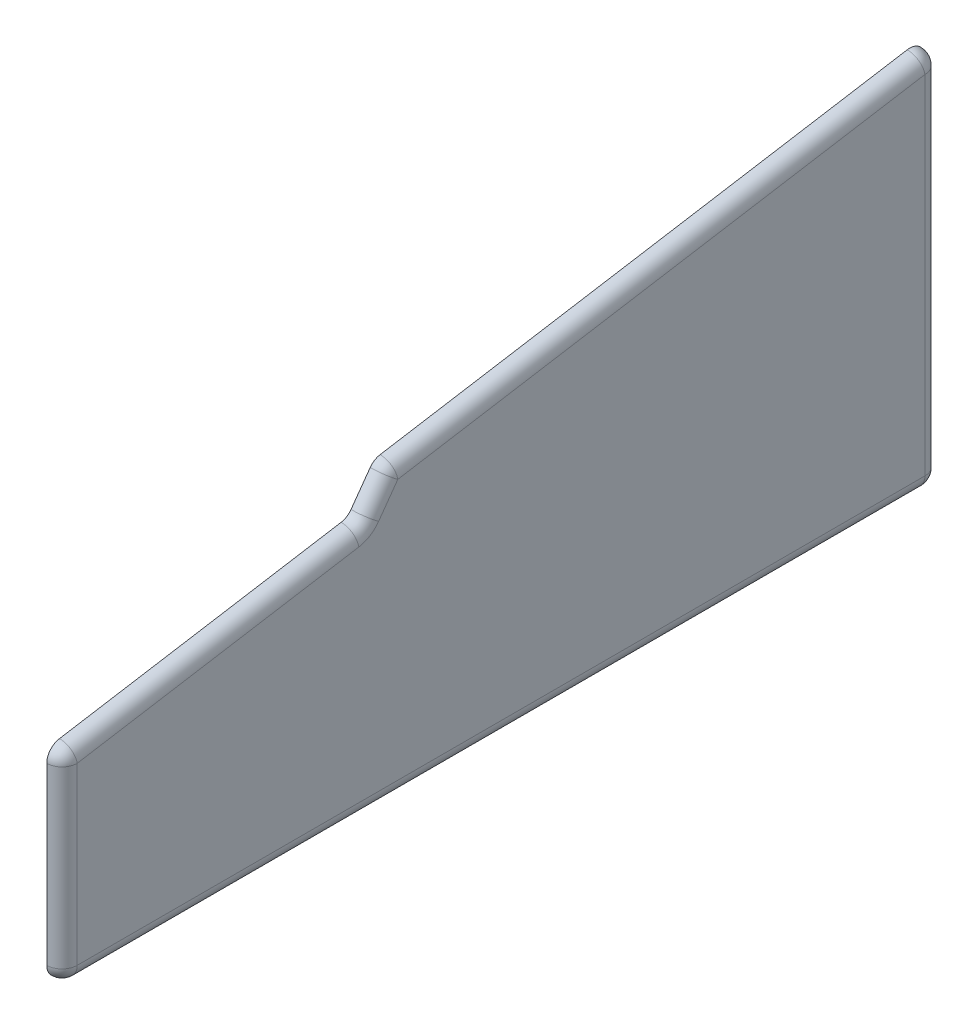
SolidWorks part; units mm, degrees
note: The reader was unsure of these and kept them because the rebuilt part matched: shared geometry of "Sketch1<4>".
ref_plane "Front Plane" through (0, 0, 0) normal (0, 0, 1) x (1, 0, 0)
ref_plane "Top Plane" through (0, 0, 0) normal (0, 1, 0) x (1, 0, 0)
ref_plane "Right Plane" through (0, 0, 0) normal (1, 0, 0) x (0, 0, -1)
sketch "Sketch1" plane through (-329.9746, 0, 0) normal (-1, 0, 0) x (0, 0, 1)
  line L0 (-32.649, -10.2195) -> (-32.649, -17.2195)
  line L1 (-29.649, -20.2195) -> (137.305, -20.2195)
  line L2 (140.305, -17.2195) -> (140.305, -10.2195)
  line L3 (-26.049, -0.2195) -> (-22.049, -0.2195) construction
  line L4 (-22.049, -0.2195) -> (-22.049, -17.2195) construction
  line L5 (-22.049, -17.2195) -> (129.705, -17.2195) construction
  line L6 (129.705, -17.2195) -> (129.705, -0.2195) construction
  line L7 (129.705, -0.2195) -> (133.705, -0.2195) construction
  line L8 (-29.649, -0.2195) -> (-32.649, -0.2195) construction
  line L9 (32.683, -17.2195) -> (32.683, -20.2195) construction
  line L10 (-29.449, -0.0195) -> (-29.449, 47.7081)
  line L11 (-26.1927, 50.4707) -> (74.0512, 33.9125)
  line L12 (74.0512, 33.9125) -> (79.2779, 26.6175)
  line L13 (79.2779, 26.6175) -> (134.7613, 17.4528)
  line L14 (137.105, 14.6903) -> (137.105, -0.0195)
  line L15 (137.105, -0.0195) -> (133.705, -0.0195)
  line L16 (74.6544, 37.0563) -> (-29.1601, 54.2042)
  line L17 (-32.649, 51.2443) -> (-32.649, -10.2195)
  line L18 (-32.649, -10.2195) -> (-26.049, -10.2195)
  line L19 (-26.049, -10.2195) -> (-26.049, -0.2195)
  line L20 (-26.049, -0.2195) -> (-29.649, -0.2195)
  line L21 (-29.649, -0.2195) -> (-29.649, 51.2443)
  line L22 (-29.649, 51.2443) -> (74.1655, 34.0964)
  line L23 (74.1655, 34.0964) -> (79.3922, 26.8013)
  line L24 (79.3922, 26.8013) -> (137.305, 17.2354)
  line L25 (137.305, 17.2354) -> (137.305, -0.2195)
  line L26 (137.305, -0.2195) -> (133.705, -0.2195)
  line L27 (133.705, -0.2195) -> (133.705, -10.2195)
  line L28 (133.705, -10.2195) -> (140.305, -10.2195)
  line L29 (140.305, -10.2195) -> (140.305, 17.2354)
  line L30 (137.7939, 20.1953) -> (82.3332, 29.3562)
  line L31 (80.3834, 30.5688) -> (76.6042, 35.8436)
  line L32 (74.6544, 37.0563) -> (-29.1601, 54.2042)
  line L33 (-32.649, 51.2443) -> (-32.649, -10.2195)
  line L35 (-26.049, -10.2195) -> (-26.049, -0.2195) construction
  line L36 (-26.049, -0.2195) -> (-29.649, -0.2195) construction
  line L37 (-29.649, -0.2195) -> (-29.649, 51.2443) construction
  line L38 (-29.649, 51.2443) -> (74.1655, 34.0964) construction
  line L39 (74.1655, 34.0964) -> (79.3922, 26.8013) construction
  line L40 (79.3922, 26.8013) -> (137.305, 17.2354) construction
  line L41 (137.305, 17.2354) -> (137.305, -0.2195) construction
  line L42 (137.305, -0.2195) -> (133.705, -0.2195) construction
  line L43 (133.705, -0.2195) -> (133.705, -10.2195) construction
  line L45 (140.305, -10.2195) -> (140.305, 17.2354)
  line L46 (137.7939, 20.1953) -> (82.3332, 29.3562)
  line L47 (80.3834, 30.5688) -> (76.6042, 35.8436)
  line L48 (129.505, -0.0195) -> (133.705, -0.0195)
  line L49 (129.505, -17.0195) -> (129.505, -0.0195)
  line L50 (-21.849, -17.0195) -> (129.505, -17.0195)
  line L51 (-21.849, -0.0195) -> (-21.849, -17.0195)
  line L52 (-26.049, -0.0195) -> (-21.849, -0.0195)
  line L53 (-26.049, -0.0195) -> (-29.449, -0.0195)
  line L54 (-29.649, -20.2195) -> (148.1639, -20.2195) construction
  arc A0 (-26.1927, 50.4707) -> (-29.449, 47.7081) centre (-26.649, 47.7081) ccw
  arc A1 (137.105, 14.6903) -> (134.7613, 17.4528) centre (134.305, 14.6903) ccw
  arc A2 (140.305, -17.2195) -> (137.305, -20.2195) centre (137.305, -17.2195) cw
  arc A3 (-32.649, -17.2195) -> (-29.649, -20.2195) centre (-29.649, -17.2195) ccw
  arc A4 (148.1639, -20.2195) -> (151.1639, -17.2195) centre (148.1639, -17.2195) ccw construction
  arc A5 (-32.649, -17.2195) -> (-29.649, -20.2195) centre (-29.649, -17.2195) ccw construction
  arc A6 (-29.1601, 54.2042) -> (-32.649, 51.2443) centre (-29.649, 51.2443) ccw
  arc A9 (140.305, 17.2354) -> (137.7939, 20.1953) centre (137.305, 17.2354) ccw
  arc A10 (80.3834, 30.5688) -> (82.3332, 29.3562) centre (82.8221, 32.3161) ccw
  arc A11 (76.6042, 35.8436) -> (74.6544, 37.0563) centre (74.1655, 34.0964) ccw
  arc A12 (-29.1601, 54.2042) -> (-32.649, 51.2443) centre (-29.649, 51.2443) ccw
  arc A15 (140.305, 17.2354) -> (137.7939, 20.1953) centre (137.305, 17.2354) ccw
  arc A16 (80.3834, 30.5688) -> (82.3332, 29.3562) centre (82.8221, 32.3161) ccw
  arc A17 (76.6042, 35.8436) -> (74.6544, 37.0563) centre (74.1655, 34.0964) ccw
  arc A26 (-29.649, 51.2443) -> (-29.649, 51.2443) centre (-26.649, 47.7081) ccw construction
  arc A27 (137.305, 17.2354) -> (137.305, 17.2354) centre (134.305, 14.6903) ccw construction
  dimension "D2" = 4
  dimension "D1" = 0
  dimension "D3" = 0.2
extrude "Boss-Extrude1" add sketch "Sketch1" against normal blind 2 contours L14 A1 L13 L12 L11 A0 L10 L53 L52 L51 L50 L49 L48 L15
extrude "Boss-Extrude2" add sketch "Sketch1<4>" along normal blind 3
sketch "Sketch1<4>" plane through (-329.9746, 0, 0) normal (-1, 0, 0) x (0, 0, 1) same geometry as "Sketch1"
fillet "Fillet1" radius 3 12 edges at (-332.9746, 17.0124, -32.649) (-332.9746, 53.532, -31.5898) (-332.9746, 45.6302, 22.7472) (-332.9746, 36.6439, 75.7499) (-332.9746, 33.2062, 78.4938) (-332.9746, 29.7686, 81.2377) (-332.9746, 24.7757, 110.0635) (-332.9746, 19.1762, 139.5927) (-332.9746, 0.0079, 140.305) (-332.9746, -19.3408, 139.4263) (-332.9746, -20.2195, 53.828) (-332.9746, -19.3408, -31.7703)
mirror "Mirror1" about plane through (-327.9746, 0, 0) normal (-1, 0, 0) of bodies 102
delete or keep bodies "Keep Left" [suppressed] type keep bodies bodies 102
delete or keep bodies "Keep Right" type delete bodies bodies 102
